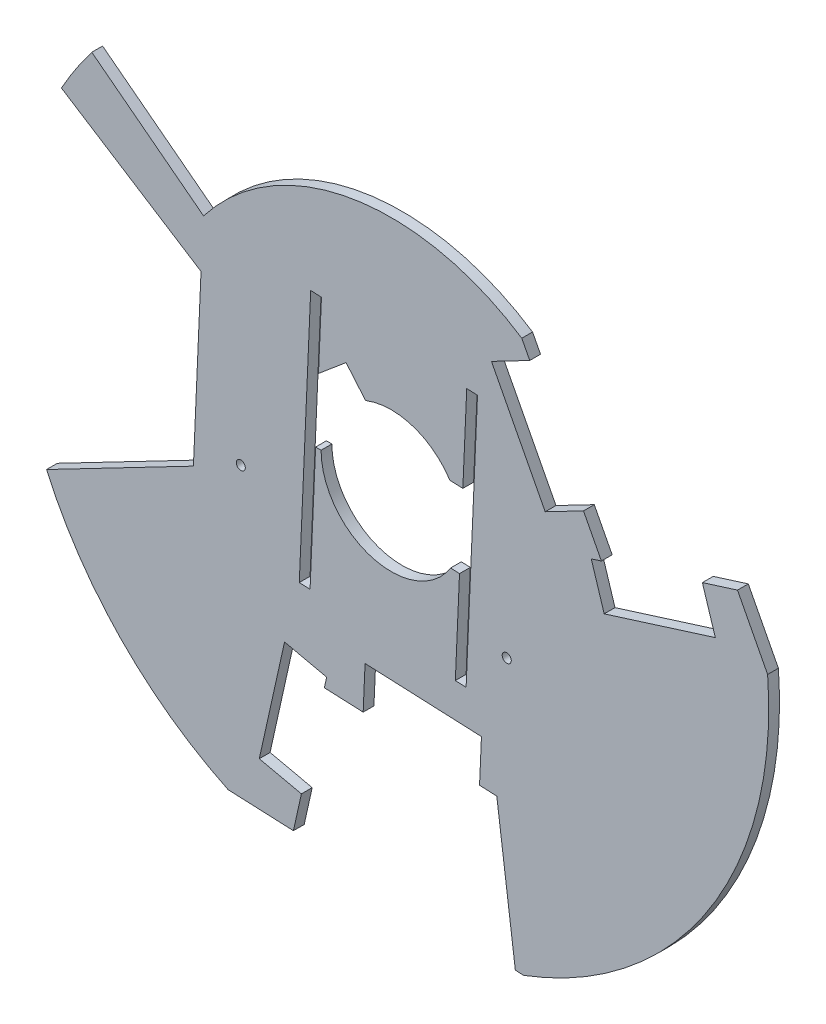
SolidWorks part; units mm, degrees
material "Balsa"
ref_plane "Plan de face" through (0, 0, 0) normal (0, 0, 1) x (1, 0, 0)
ref_plane "Plan de dessus" through (0, 0, 0) normal (0, 1, 0) x (1, 0, 0)
ref_plane "Plan de droite" through (0, 0, 0) normal (1, 0, 0) x (0, 0, -1)
sketch "Esquisse1" plane through (0, 0, 0) normal (0, 0, 1) x (1, 0, 0)
  line L0 (-11.9, 30.243) -> (-20.9197, 40.9503)
  line L1 (0, 0) -> (31.6699, 0) construction
  line L2 (-20.9197, 40.9503) -> (-33.7021, 30.1824)
  line L3 (174.4814, 13.462) -> (160.5092, 40.3333)
  line L4 (0, 0) -> (0, 32.5) construction
  line L5 (35.6001, -41.61) -> (34.7183, -61.5906) construction
  line L6 (-41.7246, -38.1976) -> (-36.7295, -38.418) construction
  line L7 (-41.7246, -38.1976) -> (-41.2837, -28.2073) construction
  line L8 (-41.2837, -28.2073) -> (-36.2886, -28.4277) construction
  line L9 (-36.7295, -38.418) -> (-36.2886, -28.4277) construction
  line L10 (34.7183, -61.5906) -> (40.0089, 58.2928)
  line L11 (-38.9773, 25.7386) -> (-11.9, 30.243) construction
  line L12 (-29.9576, 15.0314) -> (-20.9197, 40.9503) construction
  line L13 (0, 0) -> (-25.4386, 27.9908) construction
  line L14 (34.7183, -61.5906) -> (29.7232, -61.3701)
  line L15 (40.0089, 58.2928) -> (35.0138, 58.5132)
  line L16 (30.605, -41.3896) -> (35.6001, -41.61) construction
  line L17 (30.605, -41.3896) -> (31.0459, -31.3993) construction
  line L18 (35.6001, -41.61) -> (36.041, -31.6197) construction
  line L19 (31.0459, -31.3993) -> (36.041, -31.6197) construction
  line L20 (29.7232, -61.3701) -> (31.6607, -17.466)
  line L21 (-37.6113, -58.3986) -> (-42.6064, -58.1781)
  line L22 (-37.6113, -58.3986) -> (-35.0341, 0)
  line L23 (-42.6064, -58.1781) -> (-37.3158, 61.7052)
  line L24 (39.1272, 38.3122) -> (34.132, 38.5327) construction
  line L25 (39.1272, 38.3122) -> (38.6863, 28.3219) construction
  line L26 (34.132, 38.5327) -> (33.6911, 28.5424) construction
  line L27 (38.6863, 28.3219) -> (33.6911, 28.5424) construction
  line L28 (-32.3207, 61.4847) -> (-37.3158, 61.7052)
  line L29 (-38.9068, 25.6548) -> (-38.9773, 25.7386) construction
  line L30 (-38.9002, 25.8036) -> (-38.9773, 25.7386) construction
  line L31 (-33.7021, 30.1824) -> (-32.3207, 61.4847)
  line L32 (-33.2024, 41.5042) -> (-38.1976, 41.7246) construction
  line L33 (-33.2024, 41.5042) -> (-33.6433, 31.5139) construction
  line L34 (-38.1976, 41.7246) -> (-38.6385, 31.7344) construction
  line L35 (-33.6433, 31.5139) -> (-38.6385, 31.7344) construction
  line L36 (33.2038, 17.5) -> (35.0138, 58.5132)
  line L37 (-32.5, 0) -> (-35.0341, 0)
  line L38 (27.2154, 17.7643) -> (33.2038, 17.5)
  line L39 (27.5233, -17.2834) -> (31.6607, -17.466)
  line L40 (-38.1976, 41.7246) -> (39.1272, 38.3122) construction
  line L41 (-38.1976, 41.7246) -> (-41.7246, -38.1976) construction
  line L42 (39.1272, 38.3122) -> (35.6001, -41.61) construction
  line L43 (-41.7246, -38.1976) -> (35.6001, -41.61) construction
  line L44 (160.5092, 40.3333) -> (97.4284, 20.4765)
  line L45 (97.4284, 20.4765) -> (60.5218, 91.4547)
  line L46 (60.5218, 91.4547) -> (113.0069, 131.6888)
  line L47 (113.0069, 131.6888) -> (111.2327, 135.101)
  line L49 (61.3846, -163.8808) -> (57.5424, -163.7113)
  line L50 (57.5424, -163.7113) -> (48.9412, -98.1408)
  line L51 (48.9412, -98.1408) -> (-30.981, -94.6137)
  line L52 (-30.981, -94.6137) -> (-45.325, -159.1716)
  line L53 (-45.325, -159.1716) -> (-75.5823, -157.8364)
  arc A0 (111.2327, 135.101) -> (-75.5823, -157.8364) centre (0, 0) ccw
  arc A1 (-32.5, 0) -> (27.5233, -17.2834) centre (0, 0) ccw
  arc A2 (27.2154, 17.7643) -> (-11.9, 30.243) centre (0, 0) ccw
  arc A3 (61.3846, -163.8808) -> (174.4814, 13.462) centre (0, 0) ccw
  circle A4 centre (121.4843, 17.5652) radius 4.7
  circle A5 centre (67.7962, 55.7884) radius 4.7
  circle A6 centre (14.4161, -86.6074) radius 4.7
  circle A7 centre (-45.5303, -113.9911) radius 4.7
  dimension "D1" = 65
  dimension "D2" = 87.845
  dimension "D3" = 42.265
  dimension "D4" = 14
  dimension "D5" = 10
  dimension "D6" = 57.18
  dimension "D7" = 5
  dimension "D8" = 20
  dimension "D9" = 20
  dimension "D11" = 35
  dimension "D12" = 17.5
extrude "Boss.-Extru.1" add sketch "Esquisse1" along normal blind 5 contours A0 A2 L36 L15 L10 L14 L20 A1 L22 L21 L23 L29 L30 L28 L31 L2 L0 region at (143.4418, -91.4771, 0)
sketch "Esquisse2" plane through (0, 0, 5) normal (0, 0, 1) x (1, 0, 0)
  line L0 (-88.149, 43.929) -> (-152.8606, 85.1976)
  line L1 (-88.149, 43.929) -> (-91.676, -35.9932)
  line L2 (-91.676, -35.9932) -> (-159.7715, -71.4008)
  line L3 (0, 0) -> (0, 85.1976) construction
  line L5 (0, 0) -> (-89.9125, 3.9679) construction
  circle A0 centre (0, 0) radius 175 construction
  arc A1 (-152.8606, 85.1976) -> (-159.7715, -71.4008) centre (0, 0) ccw
  dimension "D1" = 90
  dimension "D2" = 80
  dimension "D3" = 120
  dimension "D4" = 87.473
extrude "Enlèv. mat.-Extru.1" cut sketch "Esquisse2" against normal blind 10
sketch "Esquisse3" plane through (0, 0, 5) normal (0, 0, 1) x (1, 0, 0)
  line L0 (14.4161, -86.6074) -> (41.3898, -87.7978) construction
  line L1 (48.9412, -98.1408) -> (-30.981, -94.6137) construction
  line L2 (40.949, -97.7881) -> (-12.9985, -95.4073)
  line L3 (40.949, -97.7881) -> (41.8307, -77.8075)
  line L4 (-12.9985, -95.4073) -> (-12.1168, -75.4267)
  line L5 (41.8307, -77.8075) -> (-12.1168, -75.4267)
  line L6 (-45.5303, -113.9911) -> (-39.6741, -87.6339) construction
  line L7 (-30.981, -94.6137) -> (-45.325, -159.1716) construction
  line L8 (-49.436, -85.4649) -> (-29.9121, -89.8028)
  line L9 (-49.436, -85.4649) -> (-61.1485, -138.1794)
  line L10 (-29.9121, -89.8028) -> (-41.6246, -142.5173)
  line L11 (-61.1485, -138.1794) -> (-41.6246, -142.5173)
  line L12 (64.2125, 84.3569) -> (89.1244, 36.4466)
  line L13 (64.2125, 84.3569) -> (46.4679, 75.1302)
  line L14 (89.1244, 36.4466) -> (71.3799, 27.2199)
  line L15 (46.4679, 75.1302) -> (71.3799, 27.2199)
  line L16 (98.7328, -0.0804) -> (92.7276, 18.9968)
  line L17 (98.7328, -0.0804) -> (150.2411, 16.1336)
  line L18 (92.7276, 18.9968) -> (144.2359, 35.2107)
  line L19 (150.2411, 16.1336) -> (144.2359, 35.2107)
  line L20 (67.7962, 55.7884) -> (55.3402, 79.7435) construction
  line L21 (121.4843, 17.5652) -> (95.7302, 9.4582) construction
  line L22 (160.5092, 40.3333) -> (97.4284, 20.4765) construction
  line L23 (97.4284, 20.4765) -> (60.5218, 91.4547) construction
  point P33 (0, 0)
  dimension "D1" = 20
  dimension "D2" = 54
  dimension "D3" = 27
  dimension "D4" = 20
  dimension "D5" = 54
  dimension "D6" = 27
  dimension "D7" = 2
extrude "Enlèv. mat.-Extru.2" cut sketch "Esquisse3" against normal blind 10
sketch "Esquisse4" plane through (0, 0, 5) normal (0, 0, 1) x (1, 0, 0)
  line L0 (-138.7868, 106.5984) -> (-86.9733, 66.8018)
  line L1 (-88.149, 43.929) -> (-152.8606, 85.1976) construction
  line L2 (60.5218, 91.4547) -> (113.0069, 131.6888) construction
  line L3 (60.5218, 91.4547) -> (113.0069, 131.6888)
  line L4 (113.0069, 131.6888) -> (111.2327, 135.101)
  line L5 (113.0069, 131.6888) -> (111.2327, 135.101) construction
  arc A0 (111.2327, 135.101) -> (-152.8606, 85.1976) centre (0, 0) ccw construction
  arc A1 (-86.9733, 66.8018) -> (60.5218, 91.4547) centre (0, 0) cw
  arc A2 (-138.7868, 106.5984) -> (111.2327, 135.101) centre (0, 0) cw
  dimension "D1" = 5
extrude "Enlèv. mat.-Extru.3" cut sketch "Esquisse4" against normal blind 10
hole_wizard "Trou taraudé M51" positions "Esquisse5" profile "Esquisse6" tap size "M5" standard "ISO" end condition through all
sketch "Esquisse5" plane through (0, 0, 5) normal (0, 0, 1) x (0.999, -0.0441, 0)
  point P0 (-68.569, -27.6625)
  point P2 (55.2809, -37.9834)
  point P4 (-87.2993, 135.5593)
sketch "Esquisse6" plane through (-69.7219, -24.6126, 5) normal (1, 0, 0) x (0, -1, 0)
  line L0 (0, 0) -> (0, 5)
  line L1 (0, 5) -> (2.1, 5)
  line L2 (2.1, 5) -> (2.1, 0)
  line L3 (2.1, 0) -> (0, 0)
  line L4 (0, -6.35) -> (0, 107.95) construction
  dimension "Diamètre principal du filetage" = 4.2
  dimension "Profondeur du trou pour taraudage jusqu'au prochain" = 5
